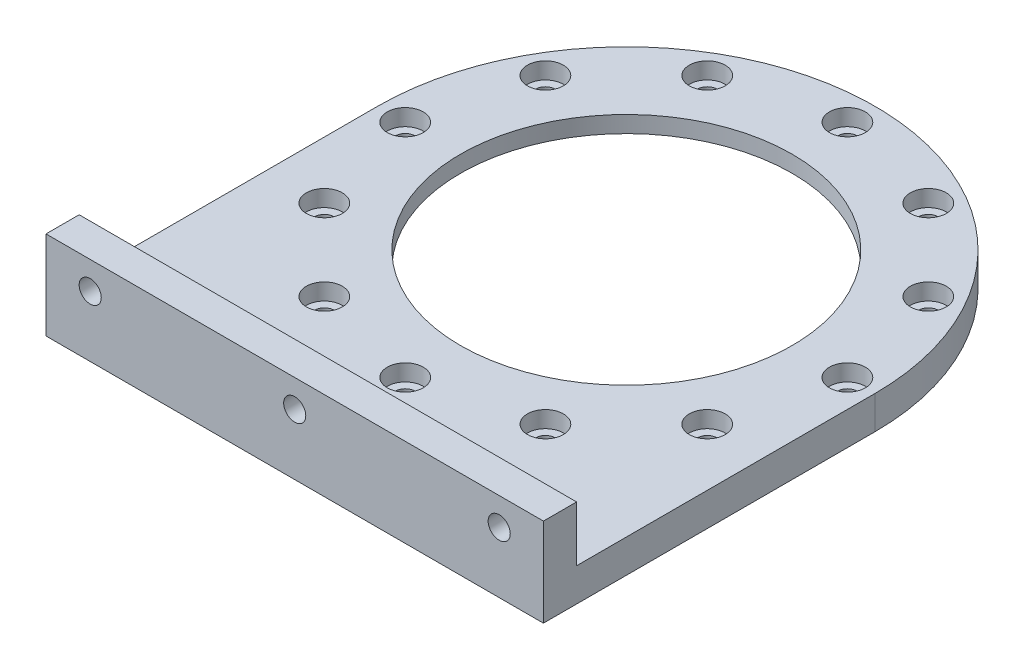
SolidWorks part; units mm, degrees
ref_plane "Front Plane" through (0, 0, 0) normal (0, 0, 1) x (1, 0, 0)
ref_plane "Top Plane" through (0, 0, 0) normal (0, 1, 0) x (1, 0, 0)
ref_plane "Right Plane" through (0, 0, 0) normal (1, 0, 0) x (0, 0, -1)
sketch "Sketch1" plane through (0, 0, 0) normal (0, 1, 0) x (1, 0, 0)
  line L0 (0, 0) -> (0, 52.0165) construction
  circle A0 centre (0, 0) radius 45
  circle A1 centre (0, 0) radius 30
  circle A2 centre (0, 0) radius 40 construction
  circle A3 centre (0, 40) radius 1.75
  circle A4 centre (0, 0) radius 36 construction
  circle A5 centre (20, 34.641) radius 1.75
  circle A6 centre (34.641, 20) radius 1.75
  circle A7 centre (40, 0) radius 1.75
  circle A8 centre (34.641, -20) radius 1.75
  circle A9 centre (20, -34.641) radius 1.75
  circle A10 centre (0, -40) radius 1.75
  circle A11 centre (-20, -34.641) radius 1.75
  circle A12 centre (-34.641, -20) radius 1.75
  circle A13 centre (-40, 0) radius 1.75
  circle A14 centre (-34.641, 20) radius 1.75
  circle A15 centre (-20, 34.641) radius 1.75
  point P21 (0, 0)
  point P34 (0, 0)
  point P48 (0, 0)
  point P72 (0, 0)
  dimension "D1" = 90
  dimension "D2" = 60
  dimension "D4" = 3.5
  dimension "D5" = 72
  dimension "D6" = 12
  dimension "D3" = 80
extrude "Boss-Extrude1" add sketch "Sketch1" along normal blind 6
sketch "Sketch2" plane through (0, 0, 0) normal (0, -1, 0) x (1, 0, 0)
  circle A0 centre (0, 0) radius 36
  dimension "D1" = 72
extrude "Cut-Extrude1" cut sketch "Sketch2" against normal blind 3
sketch "Sketch3" plane through (0, 6, 0) normal (0, 1, 0) x (1, 0, 0)
  line L0 (0, 0) -> (49.8808, 0) construction
  circle A0 centre (40, 0) radius 3.25
  circle A1 centre (34.641, -20) radius 3.25
  circle A2 centre (20, -34.641) radius 3.25
  circle A3 centre (0, -40) radius 3.25
  circle A4 centre (-20, -34.641) radius 3.25
  circle A5 centre (-34.641, -20) radius 3.25
  circle A6 centre (-40, 0) radius 3.25
  circle A7 centre (-34.641, 20) radius 3.25
  circle A8 centre (-20, 34.641) radius 3.25
  circle A9 centre (0, 40) radius 3.25
  circle A10 centre (20, 34.641) radius 3.25
  circle A11 centre (34.641, 20) radius 3.25
  point P30 (0, 0)
  dimension "D1" = 6.5
  dimension "D2" = 12
extrude "Cut-Extrude2" cut sketch "Sketch3" against normal blind 3
sketch "Sketch4" plane through (0, 0, 0) normal (0, -1, 0) x (1, 0, 0)
  line L0 (45, 0) -> (45, 60)
  line L1 (-45, 0) -> (-45, 60)
  line L2 (45, 60) -> (-45, 60)
  line L3 (45, 0) -> (-45, 0) construction
  circle A1 centre (0, 0) radius 45 construction
  arc A2 (45, 0) -> (-45, 0) centre (0, 0) ccw
  dimension "D1" = 60
  dimension "D2" = 90
extrude "Boss-Extrude4" add sketch "Sketch4" against normal blind 6
sketch "Sketch5" plane through (0, 6, 0) normal (0, 1, 0) x (1, 0, 0)
  line L0 (-45, -60) -> (-45, 0) construction
  line L1 (-45, -54) -> (45, -54)
  line L2 (-45, -54) -> (-45, -60)
  line L3 (-45, -60) -> (45, -60)
  line L4 (45, -54) -> (45, -60)
  dimension "D1" = 6
extrude "Boss-Extrude5" add sketch "Sketch5" along normal blind 10
sketch "Sketch6" plane through (0, 0, 54) normal (0, 0, -1) x (-1, 0, 0)
  line L0 (-45, 11) -> (45, 11) construction
  line L1 (-45, 16) -> (-45, 6) construction
  line L2 (45, 16) -> (45, 6) construction
  line L3 (0, 16) -> (0, 6) construction
  line L4 (-45, 16) -> (45, 16) construction
  line L5 (-45, 6) -> (45, 6) construction
  circle A0 centre (-37, 11) radius 2
  circle A1 centre (37, 11) radius 2
  circle A2 centre (0, 11) radius 2
  dimension "D1" = 4
  dimension "D3" = 4
  dimension "D2" = 8
extrude "Cut-Extrude3" cut sketch "Sketch6" against normal blind 8
